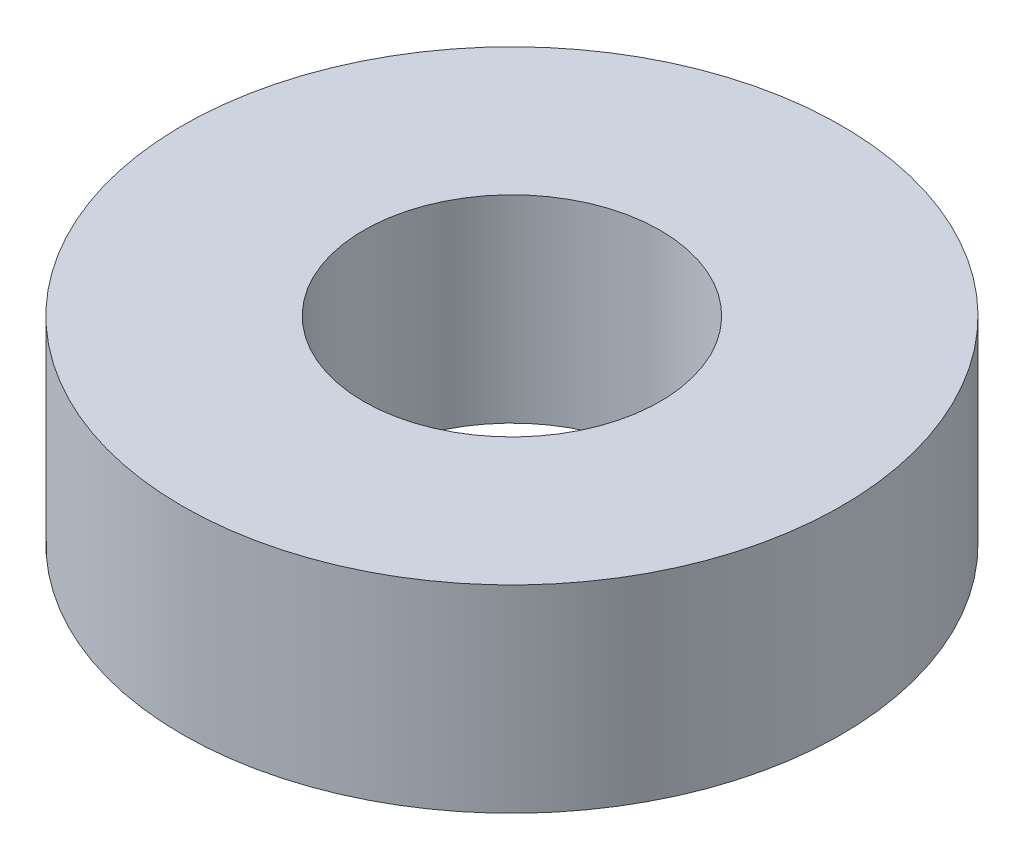
SolidWorks part; units mm, degrees
ref_plane "Front Plane" through (0, 0, 0) normal (0, 0, 1) x (1, 0, 0)
ref_plane "Top Plane" through (0, 0, 0) normal (0, 1, 0) x (1, 0, 0)
ref_plane "Right Plane" through (0, 0, 0) normal (1, 0, 0) x (0, 0, -1)
sketch "Sketch1" plane through (0, 0, 0) normal (0, 1, 0) x (1, 0, 0)
  circle A0 centre (0, 0) radius 5
  dimension "D1" = 10
extrude "Boss-Extrude1" add sketch "Sketch1" along normal blind 3
hole_wizard "M4 Clearance Hole1" positions "Sketch2" profile "Sketch4" hole size "M4" standard "ANSI Metric" end condition through all
sketch "Sketch2" plane through (0, 3, 0) normal (0, 1, 0) x (1, 0, 0)
  point P0 (0, 0)
sketch "Sketch4" plane through (0, 3, 0) normal (1, 0, 0) x (0, 0, 1)
  line L0 (0, 0) -> (0, 3)
  line L1 (0, 3) -> (2.25, 3)
  line L2 (2.25, 3) -> (2.25, 0)
  line L5 (2.25, 0) -> (0, 0)
  line L11 (0, -6.35) -> (0, 107.95) construction
  dimension "Thru Hole Dia." = 4.5
  dimension "Thru Hole Depth" = 3
